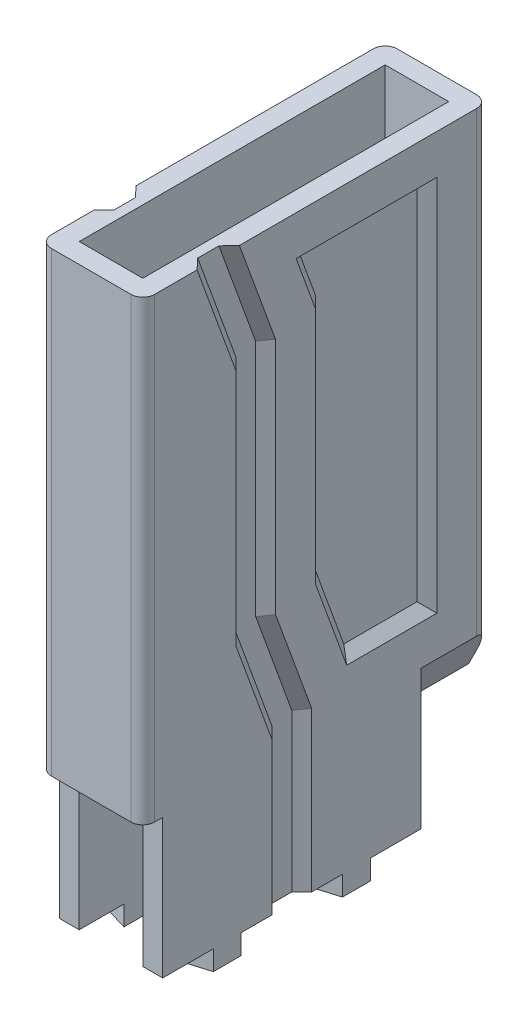
SolidWorks part; units mm, degrees
ref_plane "Front Plane" through (0, 0, 0) normal (0, 0, 1) x (1, 0, 0)
ref_plane "Top Plane" through (0, 0, 0) normal (0, 1, 0) x (1, 0, 0)
ref_plane "Right Plane" through (0, 0, 0) normal (1, 0, 0) x (0, 0, -1)
sketch "Sketch1" plane through (0, 0, 0) normal (0, 1, 0) x (1, 0, 0)
  line L0 (-13, 19.75) -> (-13, 12.75)
  line L1 (-13, -32.5) -> (13, -32.5) construction
  line L2 (-13, -32.5) -> (-13, 32.5) construction
  line L3 (-13, 32.5) -> (13, 32.5) construction
  line L4 (13, -32.5) -> (13, 32.5) construction
  line L5 (-13, -32.5) -> (13, 32.5) construction
  line L6 (-13, 32.5) -> (13, -32.5) construction
  line L7 (-13, 12.75) -> (-8, 11.25)
  line L10 (-13, 19.75) -> (-8, 21.25)
  line L11 (-8, 21.25) -> (-8, 11.25)
  line L12 (0, 0) -> (-13, 0) construction
  line L13 (0, 0) -> (0, 32.5) construction
  line L14 (-13, -19.75) -> (-8, -21.25)
  line L15 (-13, -19.75) -> (-13, -12.75)
  line L16 (-13, -12.75) -> (-8, -11.25)
  line L17 (-8, -21.25) -> (-8, -11.25)
  line L18 (13, 19.75) -> (8, 21.25)
  line L19 (13, 19.75) -> (13, 12.75)
  line L20 (13, 12.75) -> (8, 11.25)
  line L21 (8, 21.25) -> (8, 11.25)
  line L22 (13, -19.75) -> (13, -12.75)
  line L23 (13, -12.75) -> (8, -11.25)
  line L24 (8, -21.25) -> (8, -11.25)
  line L25 (13, -19.75) -> (8, -21.25)
  point P0 (0, 0)
  point P11 (-8, 16.25)
  point P14 (0, 16.25)
  dimension "D1" = 26
  dimension "D2" = 65
  dimension "D3" = 10
  dimension "D4" = 5
  dimension "D5" = 7
extrude "Boss-Extrude1" add sketch "Sketch1" against normal blind 5
sketch "Sketch3" plane through (0, 0, 0) normal (0, 1, 0) x (1, 0, 0)
  line L1 (-13, -32.5) -> (13, -32.5) construction
  line L2 (-13, -32.5) -> (-13, -89.5) construction
  line L3 (-13, -89.5) -> (57, -89.5) construction
  line L4 (57, -32.5) -> (57, -89.5) construction
  line L5 (13, -32.5) -> (13, 32.5) construction
  line L7 (57, -32.5) -> (57, -27.5) construction
  line L8 (57, -27.5) -> (13, -27.5) construction
  line L9 (13, -32.5) -> (13, -27.5) construction
  dimension "D1" = 57
  dimension "D2" = 70
  dimension "D3" = 5
sketch "Sketch5" plane through (0, 0, 0) normal (0, 1, 0) x (1, 0, 0)
  line L0 (-13, -32.5) -> (13, -32.5) construction
  line L1 (-13, 32.5) -> (-8, 32.5)
  line L2 (-13, 32.5) -> (-13, -32.5)
  line L3 (-13, -32.5) -> (-8, -32.5)
  line L4 (-8, 32.5) -> (-8, -32.5)
  line L5 (-8, -21.25) -> (-8, -11.25) construction
  line L6 (8, -21.25) -> (8, -11.25) construction
  line L7 (13, 32.5) -> (8, 32.5)
  line L8 (13, 32.5) -> (13, -32.5)
  line L9 (13, -32.5) -> (8, -32.5)
  line L10 (8, 32.5) -> (8, -32.5)
extrude "Boss-Extrude6" add sketch "Sketch5" along normal blind 150
sketch "Sketch6" plane through (0, 0, -32.5) normal (0, 0, -1) x (-1, 0, 0)
  line L6 (-13, 150) -> (-13, 0) construction
  line L7 (-8, 150) -> (-13, 150)
  line L8 (-8, 150) -> (-8, 25)
  line L9 (-8, 25) -> (-13, 25)
  line L10 (-13, 150) -> (-13, 25)
  line L11 (8, 150) -> (8, 0) construction
  line L12 (13, 150) -> (8, 150)
  line L13 (13, 150) -> (13, 25)
  line L14 (13, 25) -> (8, 25)
  line L15 (8, 150) -> (8, 25)
  line L16 (13, 0) -> (-13, 0) construction
  dimension "D1" = 25
extrude "Boss-Extrude7" add sketch "Sketch6" along normal blind 12
sketch "Sketch9" plane through (0, 0, -44.5) normal (0, 0, -1) x (-1, 0, 0)
  line L1 (-13, 25) -> (13, 25)
  line L2 (-13, 25) -> (-13, 150)
  line L3 (-13, 150) -> (13, 150)
  line L4 (13, 25) -> (13, 150)
extrude "Boss-Extrude9" add sketch "Sketch9" along normal blind 5
sketch "Sketch7" plane through (0, 0, 32.5) normal (0, 0, 1) x (1, 0, 0)
  line L0 (-13, 150) -> (-13, 0) construction
  line L1 (13, 150) -> (-13, 150)
  line L2 (13, 150) -> (13, 35)
  line L3 (13, 35) -> (-13, 35)
  line L4 (-13, 150) -> (-13, 35)
  line L5 (-13, 0) -> (13, 0) construction
  dimension "D1" = 35
extrude "Boss-Extrude8" add sketch "Sketch7" along normal blind 5
sketch "Sketch10" plane through (0, 0, -32.5) normal (0, 0, -1) x (-1, 0, 0)
  line L0 (-8, 25) -> (-8, 0) construction
  line L1 (-13, 25) -> (-8, 25)
  line L2 (-13, 25) -> (-13, 15)
  line L3 (-13, 15) -> (-8, 15)
  line L4 (-8, 25) -> (-8, 15)
  line L5 (8, 25) -> (8, 0) construction
  line L6 (13, 25) -> (8, 25)
  line L7 (13, 25) -> (13, 15)
  line L8 (13, 15) -> (8, 15)
  line L9 (8, 25) -> (8, 15)
  dimension "D1" = 10
chamfer "Chamfer1" distance 10 distance2 5 1 edges at (13, 25, -41) first distance on face at (13, 25, -1.5)
chamfer "Chamfer2" distance 5 distance2 10 1 edges at (-13, 25, -41) first distance on face at (-4.3333, 25, -42.1667)
fillet "Fillet1" radius 3 4 edges at (-13, 92.5, -49.5) (13, 92.5, -49.5) (13, 92.5, 37.5) (-13, 92.5, 37.5)
sketch "Sketch13" plane through (-13, 0, 0) normal (-1, 0, 0) x (0, 0, 1)
  line L0 (13.1985, 150) -> (4.0993, 125)
  line L1 (-46.5, 150) -> (34.5, 150) construction
  line L2 (4.0993, 125) -> (4.0993, 65)
  line L3 (4.0993, 65) -> (-5, 40)
  line L4 (-5, 40) -> (-5, 0)
  line L5 (32.5, 0) -> (-32.5, 0) construction
  line L6 (23.8403, 150) -> (14.0993, 123.2367)
  line L8 (14.0993, 123.2367) -> (14.0993, 63.2367)
  line L9 (14.0993, 63.2367) -> (5, 38.2367)
  line L10 (5, 38.2367) -> (5, 0)
  line L11 (22.5954, 146.5798) -> (14.0993, 123.2367) construction
  line L12 (-5, 40) -> (-5, 0) construction
  line L13 (-5, 0) -> (5, 0)
  line L14 (23.8403, 150) -> (13.1985, 150)
  point P4 (0, 0)
  dimension "D2" = 25
  dimension "D3" = 60
  dimension "D4" = 160
  dimension "D1" = 10
extrude "Cut-Extrude2" cut sketch "Sketch13" against normal blind 2.5
sketch "Sketch15" plane through (-13, 0, 0) normal (-1, 0, 0) x (0, 0, 1)
  line L37 (-5.9007, 66.7633) -> (-14.3969, 43.4202)
  line L38 (3.8016, 153.4202) -> (-5.9007, 126.7633)
  line L39 (-5.9007, 126.7633) -> (-5.9007, 66.7633)
  line L40 (-5.9007, 66.7633) -> (-13.8219, 45)
  line L41 (-1.083, 140) -> (-5.9007, 126.7633)
  line L42 (-5.9007, 126.7633) -> (-5.9007, 66.7633)
  line L49 (-32.5, 45) -> (-36.5, 45)
  line L50 (-36.5, 45) -> (-36.5, 140)
  line L51 (-36.5, 140) -> (13.1985, 140)
  line L52 (-13.8219, 45) -> (-36.5, 45)
  line L53 (-36.5, 45) -> (-36.5, 140)
  line L54 (-36.5, 140) -> (-1.083, 140)
  point P0 (-13.8219, 46.5352)
  dimension "D1" = 10
  dimension "D2" = 10
extrude "Cut-Extrude3" cut sketch "Sketch15" against normal blind 2.5
chamfer "Chamfer3" distance 2.5 angle 45 14 edges at (-10.5, 136.6184, 18.9698) (-10.5, 93.2367, 14.0993) (-10.5, 50.7367, 9.5496) (-10.5, 19.1184, 5) (-10.5, 20, -5) (-10.5, 52.5, -0.4504) (-10.5, 95, 4.0993) (-10.5, 137.5, 8.6489) (-10.5, 45, -25.161) (-10.5, 55.8816, -9.8613) (-10.5, 96.7633, -5.9007) (-10.5, 133.3816, -3.4919) (-10.5, 92.5, -36.5) (-10.5, 140, -18.7915)
mirror "Mirror1" about plane through (0, 0, 0) normal (1, 0, 0) of "Chamfer3", "Cut-Extrude3", "Cut-Extrude2"
